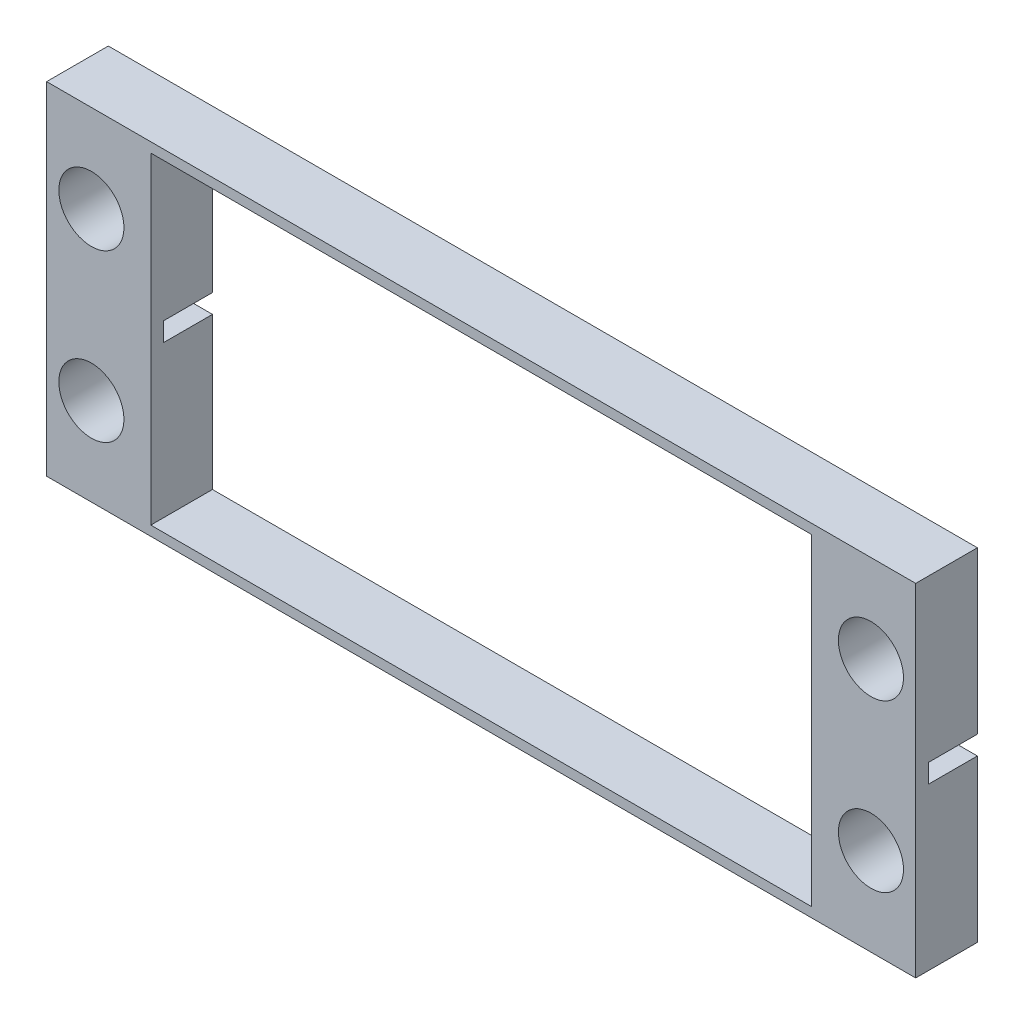
SolidWorks part; units mm, degrees
ref_plane "Front Plane" through (0, 0, 0) normal (0, 0, 1) x (1, 0, 0)
ref_plane "Top Plane" through (0, 0, 0) normal (0, 1, 0) x (1, 0, 0)
ref_plane "Right Plane" through (0, 0, 0) normal (1, 0, 0) x (0, 0, -1)
sketch "Sketch1" plane through (0, 0, 0) normal (0, 0, 1) x (1, 0, 0)
  line L1 (-26.7, -10.5) -> (26.7, -10.5)
  line L2 (-26.7, -10.5) -> (-26.7, 10.5)
  line L3 (-26.7, 10.5) -> (26.7, 10.5)
  line L4 (26.7, -10.5) -> (26.7, 10.5)
  line L5 (-26.7, -10.5) -> (26.7, 10.5) construction
  line L6 (-26.7, 10.5) -> (26.7, -10.5) construction
  point P0 (0, 0)
  dimension "D1" = 53.4
  dimension "D2" = 21
extrude "Boss-Extrude2" add sketch "Sketch1" along normal blind 3.79
sketch "Sketch3" plane through (0, 0, 3.79) normal (0, 0, 1) x (1, 0, 0)
  line L0 (0, 0) -> (0, 17.1102) construction
  line L1 (0, 0) -> (32.4612, 0) construction
  line L3 (-20.3, -9.9) -> (20.3, -9.9)
  line L4 (-20.3, -9.9) -> (-20.3, 9.9)
  line L5 (-20.3, 9.9) -> (20.3, 9.9)
  line L6 (20.3, -9.9) -> (20.3, 9.9)
  line L7 (-20.3, -9.9) -> (20.3, 9.9) construction
  line L8 (-20.3, 9.9) -> (20.3, -9.9) construction
  line L9 (-26.7, 10.5) -> (-26.7, -10.5) construction
  line L10 (26.7, 10.5) -> (-26.7, 10.5) construction
  dimension "D1" = 6.4
  dimension "D2" = 0.6
extrude "Cut-Extrude1" cut sketch "Sketch3" against normal through all
sketch "Sketch4" plane through (-26.7, 0, 0) normal (-1, 0, 0) x (0, 0, 1)
  line L0 (0, 0) -> (9.4697, 0) construction
  line L1 (0, 0.58) -> (3, 0.58)
  line L2 (0, 10.5) -> (0, -10.5) construction
  line L3 (3, 0.58) -> (3, -0.58)
  line L4 (0, 0.58) -> (0, -0.58)
  line L5 (0, -0.58) -> (3, -0.58)
  point P10 (3, 0)
  dimension "D1" = 3
  dimension "D2" = 0.58
extrude "Cut-Extrude2" cut sketch "Sketch4" against normal through all
sketch "Sketch5" plane through (0, 0, 3.79) normal (0, 0, 1) x (1, 0, 0)
  line L0 (0, 0) -> (0, 41.3476) construction
  line L1 (0, 0) -> (29.193, 0) construction
  circle A0 centre (-23.95, 5.1) radius 2
  circle A1 centre (-23.95, -5.1) radius 2
  circle A2 centre (23.95, -5.1) radius 2
  circle A3 centre (23.95, 5.1) radius 2
  point P12 (-21.95, 5.1)
  point P13 (21.95, 5.1)
  dimension "D2" = 4
  dimension "D1" = 10.2
  dimension "D3" = 43.9
extrude "Cut-Extrude3" cut sketch "Sketch5" against normal blind 6.33
